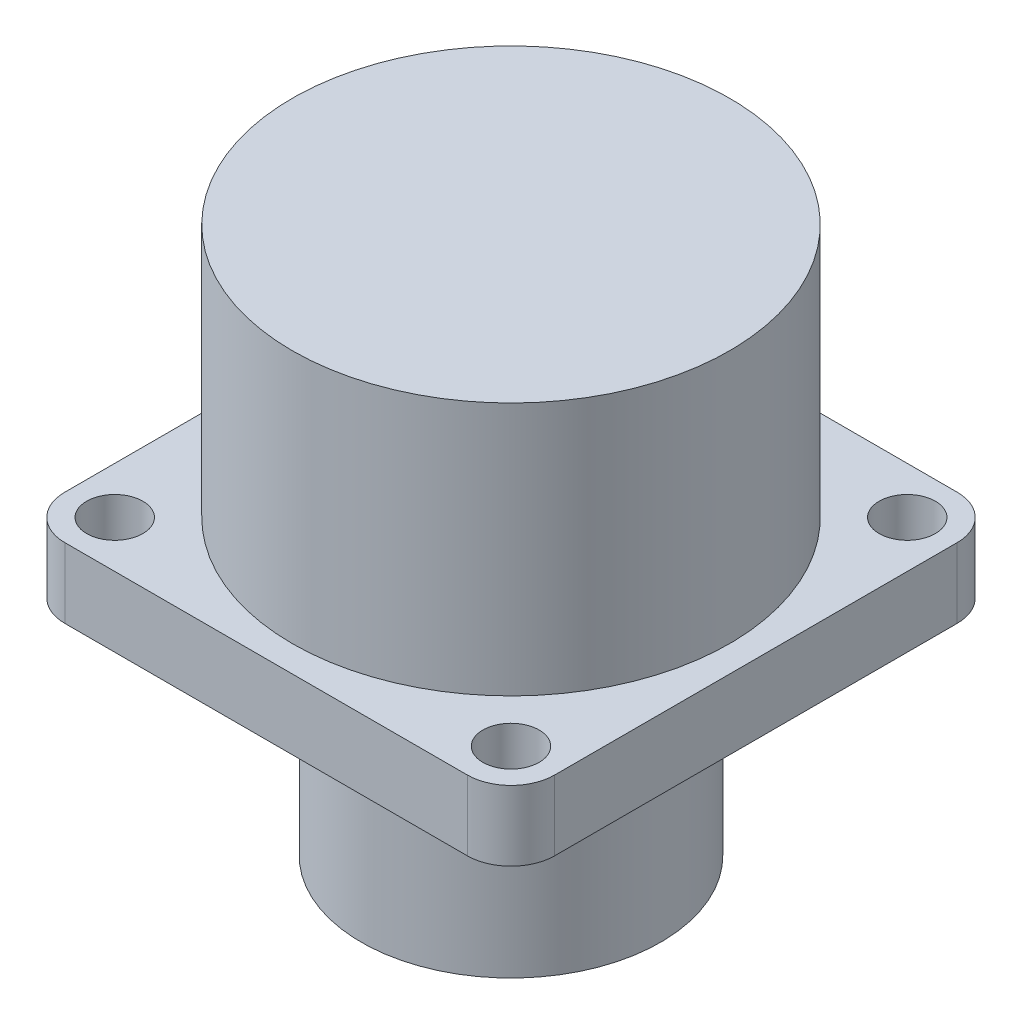
SolidWorks part; units mm, degrees
ref_plane "XY" through (0, 0, 0) normal (0, 0, 1) x (1, 0, 0)
ref_plane "XZ" through (0, 0, 0) normal (0, 1, 0) x (1, 0, 0)
ref_plane "YZ" through (0, 0, 0) normal (1, 0, 0) x (0, 0, -1)
ref_axis "X" through (-88.99, 0, 0) along (1, 0, 0)
ref_axis "Y" through (0, -55, 0) along (0, 1, 0)
ref_axis "Z" through (0, 0, 55) along (0, 0, -1)
sketch "Sketch1" plane through (0, 0, 0) normal (0, 1, 0) x (1, 0, 0)
  line L1 (-14.224, -14.224) -> (14.224, -14.224)
  line L2 (-14.224, -14.224) -> (-14.224, 14.224)
  line L3 (-14.224, 14.224) -> (14.224, 14.224)
  line L4 (14.224, -14.224) -> (14.224, 14.224)
  line L5 (-14.224, -14.224) -> (14.224, 14.224) construction
  line L6 (-14.224, 14.224) -> (14.224, -14.224) construction
  point P0 (0, 0)
  dimension "D1" = 28.448
extrude "Boss-Extrude1" add sketch "Sketch1" along normal blind 4.064
sketch "Sketch2" plane through (0, 4.064, 0) normal (0, 1, 0) x (1, 0, 0)
  circle A0 centre (0, 0) radius 12.7
  dimension "D1" = 25.4
extrude "Boss-Extrude2" add sketch "Sketch2" along normal blind 14.732
sketch "Sketch3" plane through (0, 0, 0) normal (0, -1, 0) x (1, 0, 0)
  circle A0 centre (0, 0) radius 8.6995
  dimension "D1" = 17.399
extrude "Boss-Extrude3" add sketch "Sketch3" along normal blind 12.954
hole_wizard "#4 Clearance Hole1" positions "Sketch4" profile "Sketch5" hole size "#4" standard "ANSI Inch"
sketch "Sketch4" plane through (0, 4.064, 0) normal (0, 1, 0) x (1, 0, 0)
  line L1 (-11.5062, -11.5062) -> (11.5062, -11.5062)
  line L2 (-11.5062, -11.5062) -> (-11.5062, 11.5062)
  line L3 (-11.5062, 11.5062) -> (11.5062, 11.5062)
  line L4 (11.5062, -11.5062) -> (11.5062, 11.5062)
  line L5 (-11.5062, 0) -> (11.5062, 0) construction
  point P1 (-11.5062, -11.5062)
  point P2 (11.5062, 11.5062)
  point P155 (-11.5062, 11.5062)
  point P156 (11.5062, -11.5062)
  dimension "D1" = 23.0124
sketch "Sketch5" plane through (-11.5062, 4.064, 11.5062) normal (1, 0, 0) x (0, 0, 1)
  line L0 (0, 0) -> (0, 8.6006)
  line L1 (0, 8.6006) -> (1.6319, 7.62)
  line L2 (1.6319, 7.62) -> (1.6319, 0)
  line L5 (1.6319, 0) -> (0, 0)
  line L10 (0, 8.6006) -> (-1.632, 7.62) construction
  line L11 (0, -6.35) -> (0, 107.95) construction
  dimension "Hole Dia." = 3.2639
  dimension "Hole Depth" = 7.62
  dimension "Drill Angle" = 118
fillet "Fillet1" radius 2.54 4 edges at (14.224, 2.032, 14.224) (14.224, 2.032, -14.224) (-14.224, 2.032, 14.224) (-14.224, 2.032, -14.224)
